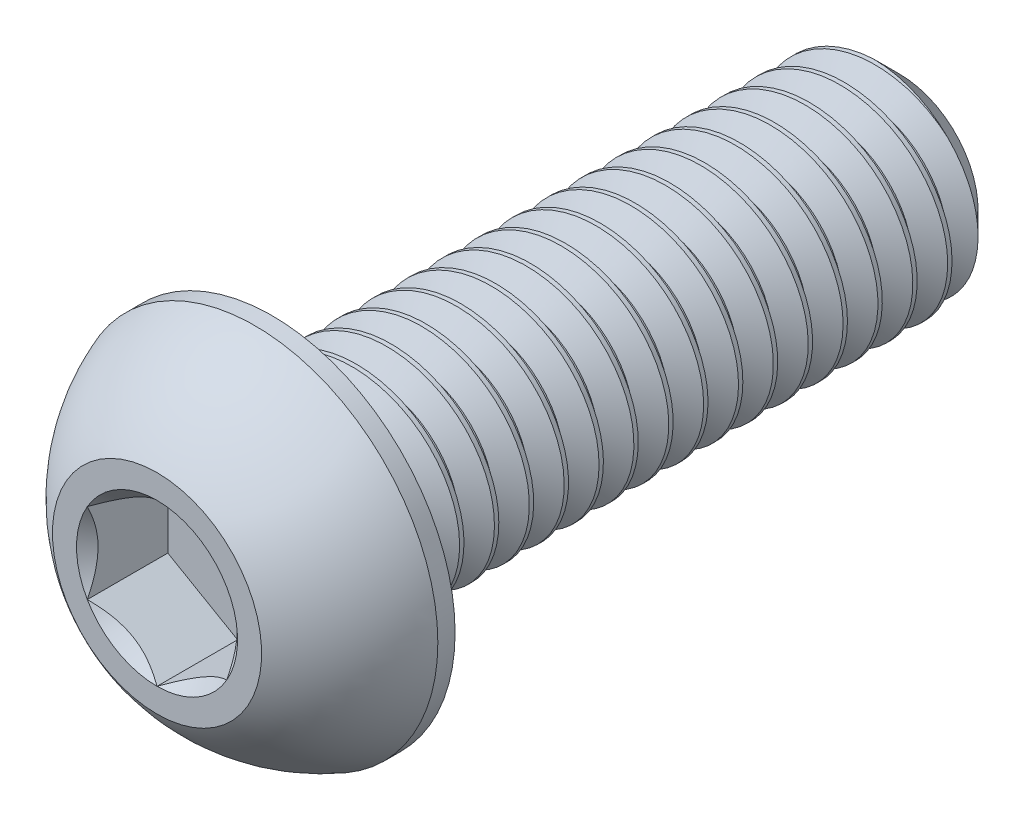
SolidWorks part; units mm, degrees
note: '?' marks a value the reader was unsure of.
ref_plane "Front" through (0, 0, 0) normal (0, 0, 1) x (1, 0, 0)
ref_plane "Top" through (0, 0, 0) normal (0, 1, 0) x (1, 0, 0)
ref_plane "Right" through (0, 0, 0) normal (1, 0, 0) x (0, 0, -1)
sketch "Sketch1" plane through (0, 0, 0) normal (1, 0, 0) x (0, 0, -1)
  line L2 (3.3, 3) -> (21.3, 3)
  line L3 (21.3, 3) -> (21.3, 0)
  line L4 (21.3, 0) -> (3.3, 0)
  line L6 (2.805, 5.25) -> (3.3, 5.25) construction
  line L7 (21.3, 3) -> (21.3, -3) construction
  line L8 (0, 0) -> (3.3, 0) construction
  line L9 (3.3, 5.25) -> (3.3, -5.25) construction
  line L11 (3.3, 3) -> (3.3, 0)
  line L13 (0, 2) -> (0, -2) construction
  line L14 (0, 2) -> (0, 3) construction
  arc A3 (0, 3) -> (2.805, 5.25) centre (4.7113, 0) cw construction
  dimension "D1" = 0.495
  dimension "Head Ht" = 3.3
  dimension "Head Dia" = 10.5
  dimension "Dia" = 6
  dimension "Lg" = 18
  dimension "Hex" = 4
revolve "Revolve1" add sketch "Sketch1" angle 360 mid plane about L4
sketch "Sketch3" plane through (0, 0, -21.3) normal (0, 0, -1) x (-1, 0, 0)
  circle A0 centre (0, 0) radius 3
curve "Helix/Spiral1" pitch 1 height 19 turns 19
chamfer "Chamfer1" distance 0.75 angle 45 1 edges at (0, 3, -21.3)
sketch "Sketch7" plane through (0, 0, 0) normal (1, 0, 0) x (0, 0, -1)
  line L6 (2.805, 5.25) -> (3.3, 5.25) construction
  line L8 (0, 0) -> (3.3, 0) construction
  line L11 (3.3, 5.25) -> (3.3, -5.25) construction
  line L12 (2.805, 5.25) -> (3.3, 5.25)
  line L13 (0, 0) -> (3.3, 0)
  line L14 (0, 2) -> (0, -2) construction
  line L15 (3.3, 5.25) -> (3.3, 0)
  line L16 (0, 3) -> (0, 0)
  arc A2 (2.805, 5.25) -> (0, 3) centre (4.7113, 0) ccw construction
  arc A3 (2.805, 5.25) -> (0, 3) centre (4.7113, 0) ccw
revolve "Revolve2" add sketch "Sketch7" angle 360 mid plane about L13
sketch "Sketch5" plane through (0, 0, 0) normal (0, 0, 1) x (1, 0, 0)
  line L1 (2, -1.1547) -> (2, 1.1547)
  line L2 (2, 1.1547) -> (0, 2.3094)
  line L3 (0, 2.3094) -> (-2, 1.1547)
  line L4 (-2, 1.1547) -> (-2, -1.1547)
  line L5 (-2, -1.1547) -> (0, -2.3094)
  line L6 (0, -2.3094) -> (2, -1.1547)
  circle A0 centre (0, 0) radius 2 construction
extrude "Cut-Extrude2" cut sketch "Sketch5" against normal blind 2.31
sketch "Sketch6" plane through (0, 0, 0) normal (0, 0, 1) x (1, 0, 0)
  circle A0 centre (0, 0) radius 2.3094
extrude "Cut-Extrude3" cut sketch "Sketch6" against normal blind 2.31 draft 45
sketch "Sketch2" plane through (0, 0, 0) normal (1, 0, 0) x (0, 0, -1)
  line L0 (20.55, 3) -> (21.425, 3)
  line L1 (21.425, 3) -> (21.05, 2.3505)
  line L2 (21.05, 2.3505) -> (20.925, 2.3505)
  line L3 (20.925, 2.3505) -> (20.55, 3)
  line L4 (20.7375, 2.6752) -> (21.2375, 2.6752) construction
  dimension "D1" = 60
  dimension "D2" = 0.125
  dimension "D3" = 0.5
sweep "Cut-Sweep1" cut profiles "Sketch2" path "Helix/Spiral1"
sketch "Sketch10" plane through (0, 0, 0) normal (1, 0, 0) x (0, 0, -1)
  line L0 (21.3, 3) -> (21.3, -3) construction
  point P0 (19.8, -3)
  dimension "D1" = 1.5
ref_axis "Center Axis 1" through (0, 0, -8.1113) along (0, 0, 1)?
ref_plane "Contact Plane 1" through (0, 0, -3.3) normal (0, 0, -1) x (-1, 0, 0)
ref_plane "Contact Plane 2" through (0, 0, 0) normal (0, 0, 1) x (1, 0, 0)
equation "\"D3@Helix/Spiral1\" = \"Lg@Sketch1\" + \"D4@Helix/Spiral1\""
equation "\"D2@Sketch2\" = \"D4@Helix/Spiral1\" * .125"
equation "\"D3@Sketch2\" = \"D4@Helix/Spiral1\" * .5"
equation "\"D1@Chamfer1\" = \"D4@Helix/Spiral1\" * .75"
equation "\"D1@Cut-Extrude2\" = \"Head Ht@Sketch1\" * .7"
equation "\"D1@Sketch1\" = \"Head Ht@Sketch1\" * .15"
equation "\"D1@Sketch10\" = \"D4@Helix/Spiral1\" * 1.5"
equation "\"D1@Cut-Extrude3\" = \"D1@Cut-Extrude2\""
